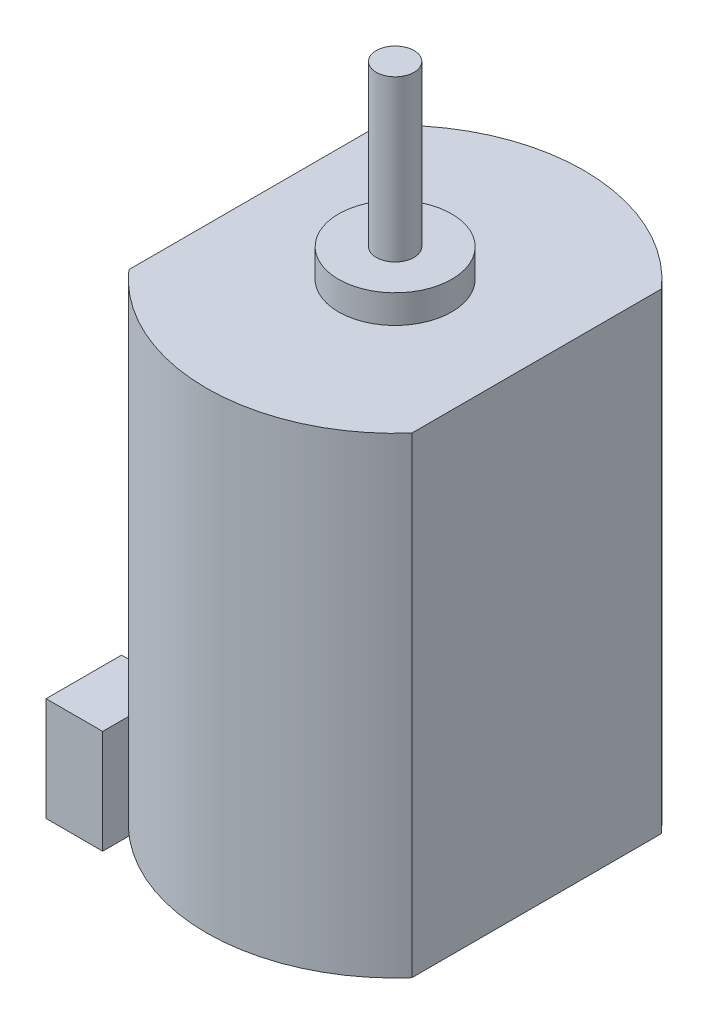
SolidWorks part; units mm, degrees
ref_plane "前视基准面" through (0, 0, 0) normal (0, 0, 1) x (1, 0, 0)
ref_plane "上视基准面" through (0, 0, 0) normal (0, 1, 0) x (1, 0, 0)
ref_plane "右视基准面" through (0, 0, 0) normal (1, 0, 0) x (0, 0, -1)
sketch "草图1" plane through (0, 0, 0) normal (0, 1, 0) x (1, 0, 0)
  circle A0 centre (0, 0) radius 10
  dimension "D1" = 20
extrude "圆柱凸台-拉伸1" add sketch "草图1" along normal blind 25
sketch "草图2" plane through (0, 0, 0) normal (0, -1, 0) x (1, 0, 0)
  line L0 (0, 0) -> (0, 8.2637) construction
  line L2 (-7.5, 10) -> (-7.5, -10)
  line L4 (7.5, 10) -> (7.5, -10)
  line L5 (7.5, 10) -> (10, 10)
  line L6 (-10, 10) -> (-7.5, 10)
  line L7 (-10, 10) -> (-10, -10)
  line L8 (-10, -10) -> (-7.5, -10)
  line L9 (10, 10) -> (10, -10)
  line L10 (7.5, -10) -> (10, -10)
  circle A0 centre (0, 0) radius 10 construction
  dimension "D1" = 15
extrude "2边切除切除-拉伸1" cut sketch "草图2" against normal up to next
sketch "草图3" plane through (0, 25, 0) normal (0, 1, 0) x (1, 0, 0)
  circle A0 centre (0, 0) radius 3
  dimension "D1" = 6
extrude "前转凸台-拉伸2" add sketch "草图3" along normal blind 1.5
sketch "草图4" plane through (0, 26.5, 0) normal (0, 1, 0) x (1, 0, 0)
  circle A0 centre (0, 0) radius 1
  dimension "D1" = 2
extrude "前转杆凸台-拉伸3" add sketch "草图4" along normal blind 10 from surface starting at face at (0, 25, 3)
sketch "草图5" plane through (0, 0, 0) normal (0, -1, 0) x (1, 0, 0)
  line L2 (4, 3) -> (4, -3)
  arc A0 (4, 3) -> (4, -3) centre (0, 0) ccw
  dimension "D1" = 10
  dimension "D2" = 4
extrude "后转凸台-拉伸4" add sketch "草图5" along normal blind 27.3 from surface starting at face at (0, 25, 3)
sketch "草图6" plane through (0, -2.3, 0) normal (0, -1, 0) x (1, 0, 0)
  circle A1 centre (0, 0) radius 1
  dimension "D1" = 2
extrude "后转杆凸台-拉伸5" add sketch "草图6" along normal blind 1
sketch "草图7" plane through (-7.5, 0, 0) normal (-1, 0, 0) x (0, 0, 1)
  line L0 (-8, 3) -> (-8, 4.5)
  line L2 (-8, 3) -> (-8, -1)
  line L3 (-8, -1) -> (-4, -1)
  line L4 (8, 3) -> (8, -1)
  line L5 (0, 0) -> (0, 3) construction
  line L9 (-4, 3) -> (-4, -1)
  line L11 (4, 3) -> (4, -1)
  line L12 (4, -1) -> (8, -1)
  line L13 (-8, 4.5) -> (-4, 4.5)
  line L14 (-4, 4.5) -> (-4, 3)
  line L15 (4, 3) -> (4, 4.5)
  line L16 (4, 4.5) -> (8, 4.5)
  line L17 (8, 4.5) -> (8, 3)
  dimension "D1" = 16
  dimension "D2" = 4
  dimension "D4" = 4
  dimension "D5" = 1.5
  dimension "D6" = 1.5
extrude "引线凸台-拉伸6" add sketch "草图7" along normal blind 3
